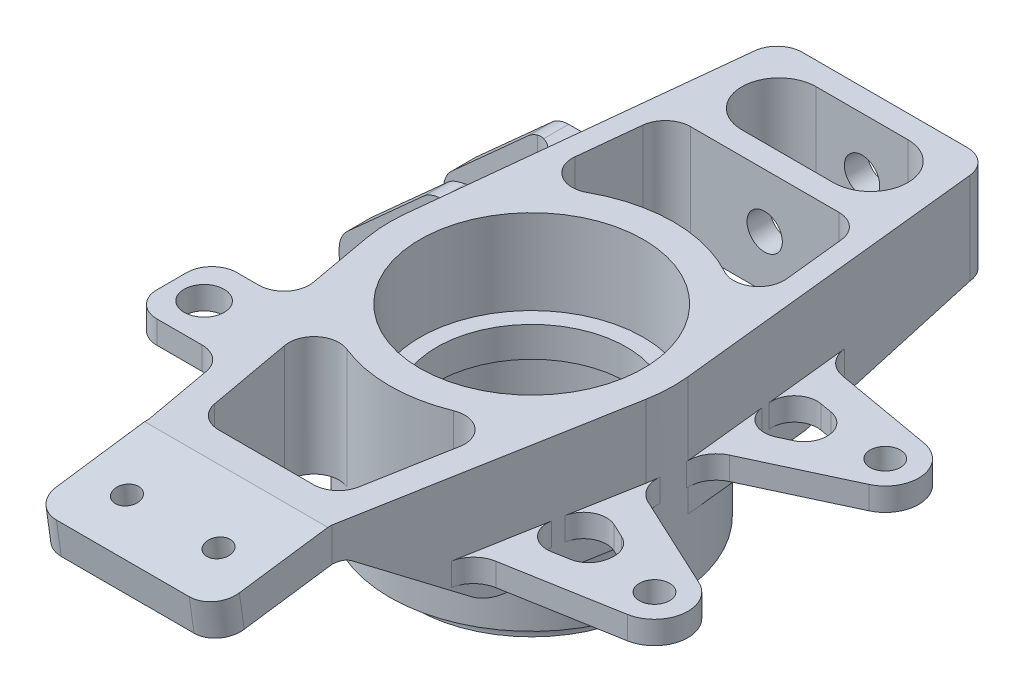
SolidWorks part; units mm, degrees
material "6061-T6 (SS)"
ref_plane "Front Plane" through (0, 0, 0) normal (0, 0, 1) x (1, 0, 0)
ref_plane "Top Plane" through (0, 0, 0) normal (0, 1, 0) x (1, 0, 0)
ref_plane "Right Plane" through (0, 0, 0) normal (1, 0, 0) x (0, 0, -1)
sketch "UBJ LBJ Geometry" plane through (0, 0, 0) normal (1, 0, 0) x (0, 0, -1)
  line L0 (0, 0) -> (0, -97.4059) construction
  line L1 (0, 0) -> (-30.7529, 0) construction
  line L2 (0, 22) -> (-45.5659, 22) construction
  line L3 (0, -10.5425) -> (-23.1063, -10.5425) construction
  line L4 (-94.107, -51.66) -> (81.28, -25.498) construction
  line L5 (0, 0) -> (0, -88.2735) construction
  line L6 (38.1, 0) -> (38.1, -66.9417) construction
  circle A0 centre (-94.107, -51.66) radius 10.3251 construction
  circle A1 centre (81.28, -25.498) radius 10.3251 construction
  dimension "D7" = 20.6502
  dimension "D8" = 20.6502
  dimension "D1" = 22
  dimension "D2" = 32.5425
  dimension "D3" = 47.498
  dimension "D4" = 73.66
  dimension "D5" = 94.107
  dimension "D6" = 81.28
  dimension "D9" = 38.1
ref_plane "Wheel Face " through (0, 22, 0) normal (0, -1, 0) x (-1, 0, 0)
ref_plane "Upright Face" through (0, -10.5425, 0) normal (0, -1, 0) x (-1, 0, 0)
ref_plane "Tie Bracket Plane" through (0, 0, -38.1) normal (0, 0, 1) x (1, 0, 0)
sketch "Tie Bracket Geometry" plane through (0, 0, -38.1) normal (0, 0, 1) x (1, 0, 0)
  line L0 (0, -31.939) -> (-65.5359, -45.8691) construction
  line L4 (0, 200000) -> (0, -200097.4059) construction
  circle A0 centre (-65.5359, -45.8691) radius 8.948 construction
  dimension "D1" = 67
  dimension "D2" = 78
sketch "Sketch1" plane through (0, 0, 0) normal (0, 0, 1) x (1, 0, 0)
  line L1 (-75.0953, -10.5425) -> (75.0953, -10.5425) construction
  line L2 (-39.37, -10.5425) -> (-39.37, -61.3425)
  line L3 (-39.37, -61.3425) -> (-32.258, -61.3425)
  line L4 (-32.258, -61.3425) -> (-32.258, -67.6925)
  line L5 (-32.258, -67.6925) -> (-30.9829, -67.6925)
  line L8 (-30.9829, -10.5425) -> (-30.9829, -34.0375)
  line L9 (-30.9829, -34.0375) -> (-26.289, -34.0375)
  line L10 (-26.289, -34.0375) -> (-26.289, -42.4195)
  line L11 (-26.289, -42.4195) -> (-30.9829, -42.4195)
  line L12 (-30.9829, -42.4195) -> (-30.9829, -67.6925)
  line L15 (-39.37, -10.5425) -> (-30.9829, -10.5425)
  line L17 (0, 0) -> (0, -23.5057) construction
  dimension "D1" = 8.382
  dimension "D2" = 61.9658
  dimension "D3" = 25.273
  dimension "D4" = 52.578
  dimension "D5" = 23.495
  dimension "D6" = 50.8
  dimension "D7" = 78.74
  dimension "D8" = 64.516
revolve "Bearing Housing Revolve" add sketch "Sketch1" angle 360 about L17
fillet "Bearing Housing Fillet" radius 6.35 1 edges at (0, -61.3425, 32.258)
sketch "Sketch2" plane through (0, -10.5425, 0) normal (0, -1, 0) x (-1, 0, 0)
  line L3 (39.37, -40.64) -> (39.37, 0)
  line L4 (-39.37, -40.64) -> (-39.37, 0)
  line L5 (39.37, -40.64) -> (-39.37, -40.64)
  circle A4 centre (0, 0) radius 39.37 construction
  arc A5 (39.37, 0) -> (-39.37, 0) centre (0, 0) cw
  dimension "D1" = 40.64
extrude "UBJ Prep" add sketch "Sketch2" along normal blind 33.02
sketch "Sketch3" plane through (-39.37, 0, 0) normal (-1, 0, 0) x (0, 0, 1)
  line L0 (-120.7672, 22) -> (120.7672, 22) construction
  line L1 (40.64, -10.5425) -> (81.931, -10.5425)
  line L2 (81.931, -10.5425) -> (113.372, -14.9612)
  line L3 (113.372, -14.9612) -> (112.0463, -24.3935)
  line L4 (112.0463, -24.3935) -> (80.6053, -19.9748)
  line L6 (40.64, -43.5625) -> (40.64, -10.5425)
  line L7 (81.931, -10.5425) -> (80.6053, -19.9748) construction
  line L8 (98.2025, -22.5188) -> (94.107, -51.66) construction
  line L9 (48.0448, -41.1804) -> (76.0192, -21.104)
  circle A0 centre (94.107, -51.66) radius 13.6189 construction
  arc A1 (40.64, -43.5625) -> (48.0448, -41.1804) centre (40.64, -30.8625) ccw
  arc A2 (80.6053, -19.9748) -> (76.0192, -21.104) centre (79.7216, -26.263) ccw
  dimension "D7" = 12.7
  dimension "D8" = 25.4
  dimension "D1" = 73.66
  dimension "D2" = 94.107
  dimension "D3" = 9.525
  dimension "D4" = 31.75
  dimension "D5" = 8
  dimension "D6" = 13.97
extrude "UBJ Extrude " add sketch "Sketch3" against normal up to surface (78.74 mm away) up to face at (39.37, -27.0525, 20.32)
sketch "Sketch4" plane through (0, -8.479, -1.1916) normal (0, -0.9903, -0.1392) x (1, 0, 0)
  line L0 (0, 114.3508) -> (0, 27.8969) construction
  line L1 (39.37, 114.3508) -> (-39.37, 114.3508) construction
  line L3 (-12.7, 100.3808) -> (12.7, 100.3808) construction
  circle A0 centre (-12.7, 100.3808) radius 3.2639
  circle A1 centre (12.7, 100.3808) radius 3.2639
  point P8 (0, 100.3808)
  dimension "D2" = 6.5278
  dimension "D1" = 25.4
  dimension "D3" = 13.97
extrude "Camber Block Holes" cut sketch "Sketch4" against normal up to surface (9.525 mm away) up to face at (0, -12.7519, 97.6515)
sketch "Sketch5" plane through (0, -43.5625, 0) normal (0, -1, 0) x (1, 0, 0)
  line L0 (-25.4, 112.0463) -> (-25.4, 80.8043)
  line L1 (25.4, 113.372) -> (39.37, 113.372)
  line L2 (39.37, 112.0463) -> (-39.37, 112.0463) construction
  line L4 (-25.4, 80.8043) -> (-38.742, 7.004)
  line L5 (25.4, 112.0463) -> (25.4, 80.8043)
  line L6 (25.4, 80.8043) -> (38.742, 7.004)
  line L7 (-25.4, 112.0463) -> (-25.4, 113.372)
  line L8 (39.37, 113.372) -> (-39.37, 113.372) construction
  line L9 (25.4, 112.0463) -> (25.4, 113.372)
  line L10 (-25.4, 113.372) -> (-39.37, 113.372)
  line L11 (-39.37, 113.372) -> (-39.37, 0)
  line L12 (39.37, 113.372) -> (39.37, 0)
  line L13 (-18.9481, 73.66) -> (18.9481, 73.66)
  line L14 (-18.9481, 73.66) -> (-27.1021, 28.5565)
  line L15 (18.9481, 73.66) -> (27.1021, 28.5565)
  arc A0 (-39.37, 0) -> (-38.742, 7.004) centre (0, 0) cw
  circle A1 centre (0, 0) radius 39.37 construction
  arc A2 (39.37, 0) -> (-39.37, 0) centre (0, 0) ccw construction
  arc A3 (39.37, 0) -> (38.742, 7.004) centre (0, 0) ccw
  arc A4 (-27.1021, 28.5565) -> (27.1021, 28.5565) centre (0, 0) cw
  point P31 (0, 73.66)
  dimension "D1" = 25.4
  dimension "D2" = 7.62
  dimension "D3" = 31.242
  dimension "D4" = 73.66
extrude "Weight Saving" cut sketch "Sketch5" against normal through all
fillet "Fillet2" radius 6.985 4 edges at (27.1021, -27.0525, 28.5565) (-27.1021, -27.0525, 28.5565) (18.9481, -16.6698, 73.66) (-18.9481, -16.6698, 73.66)
sketch "Sketch6" plane through (0, -10.5425, 0) normal (0, -1, 0) x (-1, 0, 0)
  line L0 (-39.37, 0) -> (-39.37, 40.64)
  line L1 (-39.37, 40.64) -> (39.37, 40.64)
  line L2 (39.37, 40.64) -> (39.37, 0)
  circle A0 centre (0, 0) radius 39.37 construction
  arc A1 (-39.37, 0) -> (39.37, 0) centre (0, 0) cw
  dimension "D1" = 40.64
extrude "LBJ Prep" add sketch "Sketch6" along normal blind 33.02
sketch "Sketch8" plane through (-39.37, 0, 0) normal (-1, 0, 0) x (0, 0, 1)
  line L0 (-40.64, -10.5425) -> (-97.9551, -10.5425)
  line L1 (-97.9551, -10.5425) -> (-97.9551, -35.9425)
  line L2 (-97.9551, -35.9425) -> (-91.6051, -35.9425)
  line L7 (-40.64, -43.5625) -> (-40.64, -10.5425)
  line L8 (-120.7672, 22) -> (120.7672, 22) construction
  line L9 (-91.6051, -35.9425) -> (-91.6051, -10.5425) construction
  line L10 (-91.6051, -35.9425) -> (-40.64, -43.5625)
  circle A0 centre (-81.28, -25.498) radius 10.3251 construction
  dimension "D3" = 20.6502
  dimension "D1" = 81.28
  dimension "D2" = 47.498
  dimension "D4" = 6.35
  dimension "D5" = 25.4
extrude "LBJ Area " add sketch "Sketch8" against normal up to surface (78.74 mm away) up to face at (39.37, -27.0525, -20.32)
sketch "Sketch7" plane through (0, -43.5625, 0) normal (0, -1, 0) x (1, 0, 0)
  line L0 (-12.7, -81.28) -> (12.7, -81.28) construction
  line L1 (0, -200000) -> (0, 200045.5659) construction
  line L2 (-12.7, -70.9549) -> (12.7, -70.9549)
  line L3 (-12.7, -91.6051) -> (12.7, -91.6051)
  line L4 (-29.21, -97.9551) -> (-39.1508, -4.1489)
  line L5 (39.37, -97.9551) -> (-39.37, -97.9551) construction
  line L6 (29.21, -97.9551) -> (39.1508, -4.1489)
  line L7 (-29.21, -97.9551) -> (-39.37, -97.9551)
  line L8 (-39.37, -97.9551) -> (-39.37, 0)
  line L9 (29.21, -97.9551) -> (39.37, -97.9551)
  line L10 (39.37, -97.9551) -> (39.37, 0)
  line L13 (-26.8695, -64.6049) -> (26.8695, -64.6049)
  line L14 (26.8695, -64.6049) -> (31.1666, -24.0549)
  line L15 (-26.8695, -64.6049) -> (-31.1666, -24.0549)
  arc A0 (-12.7, -70.9549) -> (-12.7, -91.6051) centre (-12.7, -81.28) ccw
  arc A1 (12.7, -91.6051) -> (12.7, -70.9549) centre (12.7, -81.28) ccw
  circle A2 centre (0, 0) radius 39.37 construction
  arc A3 (-39.37, 0) -> (39.37, 0) centre (0, 0) ccw construction
  arc A4 (39.37, 0) -> (39.1508, -4.1489) centre (0, 0) cw
  arc A5 (-39.37, 0) -> (-39.1508, -4.1489) centre (0, 0) ccw
  arc A6 (-31.1666, -24.0549) -> (31.1666, -24.0549) centre (0, 0) ccw
  point P4 (0, -81.28)
  point P28 (0, -64.6049)
  dimension "D1" = 81.28
  dimension "D2" = 20.6502
  dimension "D3" = 25.4
  dimension "D4" = 10.16
  dimension "D5" = 6.35
  dimension "D6" = 5.842
extrude "LBJ Taper And Slot" cut sketch "Sketch7" against normal up to surface (33.02 mm away) up to face at (0, -10.5425, 14.3596)
fillet "Fillet3" radius 6.985 4 edges at (26.8695, -25.2609, -64.6049) (-26.8695, -25.2609, -64.6049) (31.1666, -27.0525, -24.0549) (-31.1666, -27.0525, -24.0549)
extrude "LBJ Holes 3/8 Clearance" cut sketch "Sketch9" against normal up to surface (33.3502 mm away) up to face at (0, -25.2609, -64.6049)
sketch "Sketch9" plane through (0, 0, -97.9551) normal (0, 0, -1) x (-1, 0, 0)
  circle A0 centre (0, -25.498) radius 4.9022
  dimension "D2" = 9.8044
  dimension "D1" = 25.498
ref_plane "Brake Mounting Plane" through (0, -30.7025, 0) normal (0, 1, 0) x (1, 0, 0)
sketch "Sketch10" plane through (0, -30.7025, 0) normal (0, 1, 0) x (1, 0, 0)
  line L0 (87.9814, 0) -> (161.3053, 0) construction
  line L1 (0, 72.9505) -> (0, 47.1638) construction
  line L2 (66.04, 32) -> (66.04, -32) construction
  line L3 (69.9619, 23.5895) -> (38.6385, 8.9831)
  line L4 (39.1508, 4.1489) -> (29.21, 97.9551) construction
  line L5 (38.6385, 8.9831) -> (34.6135, 46.9645)
  line L6 (34.6135, 46.9645) -> (67.6515, 41.139)
  line L7 (69.9619, -23.5895) -> (38.404, -8.8738)
  line L8 (25.4, -80.8043) -> (38.742, -7.004) construction
  line L9 (38.404, -8.8738) -> (31.4158, -47.5283)
  line L10 (31.4158, -47.5283) -> (67.6515, -41.139)
  circle A0 centre (66.04, 32) radius 4.2
  circle A1 centre (66.04, -32) radius 4.2
  arc A2 (67.6515, -41.139) -> (69.9619, -23.5895) centre (66.04, -32) ccw
  arc A3 (69.9619, 23.5895) -> (67.6515, 41.139) centre (66.04, 32) ccw
  point P7 (66.04, 0)
  dimension "D2" = 8.4
  dimension "D3" = 5.08
  dimension "D4" = 5.08
  dimension "D1" = 64
  dimension "D5" = 66.04
  dimension "D6" = 80
  dimension "D7" = 65
  dimension "D8" = 65
  dimension "D9" = 100
extrude "Brake Mounts" add sketch "Sketch10" against normal blind 6.35
fillet "Outside Fillets" radius 7.62 4 edges at (38.404, -33.8775, 8.8738) (31.4158, -33.8775, 47.5283) (38.6385, -33.8775, -8.9831) (34.6135, -33.8775, -46.9645)
sketch "Sketch18" plane through (0, -37.0525, 0) normal (0, -1, 0) x (1, 0, 0)
  line L0 (33.1015, 38.204) -> (36.7685, 17.9202)
  line L1 (36.7685, 17.9202) -> (52.8827, 25.4343)
  line L2 (52.8827, 25.4343) -> (50.6114, 35.1165)
  line L3 (50.6114, 35.1165) -> (33.1015, 38.204)
  line L4 (37.648, -18.3303) -> (35.5884, -37.7655)
  line L5 (35.5884, -37.7655) -> (53.0983, -34.678)
  line L6 (53.0983, -34.678) -> (52.1507, -25.093)
  line L7 (52.1507, -25.093) -> (37.648, -18.3303)
  line L8 (34.009, -52.6695) -> (39.1508, -4.1489) construction
  line L9 (38.742, 7.004) -> (30.4709, 52.7547) construction
  line L10 (69.9619, 23.5895) -> (43.5656, 11.2807) construction
  line L11 (36.6462, 46.6061) -> (67.6515, 41.139) construction
  line L12 (43.5656, -11.2807) -> (69.9619, -23.5895) construction
  line L13 (67.6515, -41.139) -> (40.2634, -45.9683) construction
  dimension "D1" = 8.89
  dimension "D2" = 8.89
  dimension "D3" = 8.89
  dimension "D4" = 8.89
  dimension "D5" = 17.78
  dimension "D6" = 17.78
  dimension "D7" = 16.002
  dimension "D8" = 17.78
extrude "Inside Holes" cut sketch "Sketch18" against normal up to surface (6.35 mm away) up to face at (66.04, -30.7025, 36.2)
fillet "Inside Fillet" radius 6.35 8 edges at (35.5884, -33.8775, -37.7655) (53.0983, -33.8775, -34.678) (52.1507, -33.8775, -25.093) (37.648, -33.8775, -18.3303) (36.7685, -33.8775, 17.9202) (33.1015, -33.8775, 38.204) (52.8827, -33.8775, 25.4343) (50.6114, -33.8775, 35.1165)
sketch "Sketch12" plane through (0, 0, -38.1) normal (0, 0, 1) x (1, 0, 0)
  line L0 (0, 3.2946) -> (0, -38.5659) construction
  line L1 (-90.5661, 0) -> (-38.2005, 0) construction
  line L2 (-73.702, -10.5425) -> (-73.702, -45.8691)
  line L3 (-57.3698, -10.5425) -> (-57.3698, -45.8691)
  line L4 (-73.702, -10.5425) -> (-57.3698, -10.5425)
  line L6 (-75.0953, -10.5425) -> (75.0953, -10.5425) construction
  circle A0 centre (-65.5359, -45.8691) radius 3.2639
  arc A1 (-73.702, -45.8691) -> (-57.3698, -45.8691) centre (-65.5359, -45.8691) ccw
  dimension "D1" = 6.5278
  dimension "D2" = 4.9022
extrude "Initial Toe Bracket" add sketch "Sketch12" along normal blind 17.78 and the other way blind 17.78 separate body
sketch "Sketch13" plane through (-57.3698, 0, 0) normal (1, 0, 0) x (0, 0, -1)
  line L0 (20.32, -18.1625) -> (55.88, -18.1625)
  line L1 (55.88, -45.8691) -> (55.88, -10.5425) construction
  line L2 (55.88, -18.1625) -> (55.88, -38.4825)
  line L3 (20.32, -18.1625) -> (20.32, -38.4825)
  line L4 (200000, -10.5425) -> (-200023.1063, -10.5425) construction
  line L5 (20.32, -38.4825) -> (55.88, -38.4825)
  line L6 (20.32, -45.8691) -> (20.32, -10.5425) construction
  dimension "D1" = 7.62
  dimension "D2" = 20.32
extrude "Toe Bracket Connection to Upright" add sketch "Sketch13" along normal up to surface (23.701 mm away) up to face at (-33.648, -30.0158, -56.0755)
sketch "Sketch14" plane through (0, 0, -55.88) normal (0, 0, -1) x (-1, 0, 0)
  line L1 (57.3698, -10.5425) -> (73.702, -10.5425)
  line L2 (57.3698, -10.5425) -> (57.3698, -18.1625)
  line L3 (57.3698, -18.1625) -> (73.702, -18.1625)
  line L4 (73.702, -10.5425) -> (73.702, -18.1625)
  line L5 (73.702, -10.5425) -> (73.702, -45.8691) construction
extrude "Excess Toe Bracket Cut" cut sketch "Sketch14" against normal up to surface (35.56 mm away) up to face at (-56.4697, -29.2849, -20.32)
sketch "Sketch21" plane through (0, 0, -20.32) normal (0, 0, 1) x (1, 0, 0)
  line L1 (-39.37, -10.5425) -> (-39.37, -61.3425) construction
  line L2 (-46.355, -38.4825) -> (-57.3698, -38.4825)
  line L3 (-57.3698, -38.4825) -> (-59.8151, -51.6965)
  line L4 (-59.8151, -51.6965) -> (-46.355, -38.4825)
  arc A0 (-73.702, -45.8691) -> (-57.3698, -45.8691) centre (-65.5359, -45.8691) ccw construction
  dimension "D1" = 6.985
extrude "Extra Material" add sketch "Sketch21" against normal up to surface (35.56 mm away) up to face at (-54.9135, -35.5324, -55.88)
sketch "Sketch23" plane through (-73.702, 0, 0) normal (-1, 0, 0) x (0, 0, 1)
  line L2 (-38.1, -4.9367) -> (-38.1, -40.1578) construction
  line L4 (-20.32, -18.1625) -> (-55.88, -18.1625) construction
  line L5 (-49.276, -18.1625) -> (-26.924, -18.1625)
  line L6 (-26.924, -18.1625) -> (-26.924, -66.0195)
  line L7 (-26.924, -66.0195) -> (-49.276, -66.0195)
  line L8 (-49.276, -66.0195) -> (-49.276, -18.1625)
  point P4 (-38.1, -18.1625)
  point P10 (-38.1, -18.1625)
  dimension "D1" = 22.352
extrude "Slot Clearning" cut sketch "Sketch23" against normal blind 33.02
sketch "Sketch26" plane through (0, 0, -20.32) normal (0, 0, 1) x (1, 0, 0)
  line L0 (-73.702, -41.0225) -> (-48.302, -18.1625)
  line L1 (-73.702, -18.1625) -> (-73.702, -45.8691) construction
  line L2 (-37.4371, -18.1625) -> (-73.702, -18.1625) construction
  line L3 (-48.302, -18.1625) -> (-73.702, -18.1625)
  line L4 (-73.702, -18.1625) -> (-73.702, -41.0225)
  circle A0 centre (-65.5359, -45.8691) radius 8.1661 construction
  arc A1 (-73.702, -45.8691) -> (-59.8151, -51.6965) centre (-65.5359, -45.8691) ccw construction
  dimension "D1" = 22.86
  dimension "D2" = 25.4
extrude "Cut-Extrude3" cut sketch "Sketch26" against normal up to surface (35.56 mm away) up to face at (-53.8081, -35.912, -55.88)
fillet "Toe Bracket Fillet" radius 6.985 2 edges at (-33.6688, -28.3225, -55.88) (-37.4371, -28.3225, -20.32)
sketch "Sketch19" plane through (0, -18.1625, 0) normal (0, 1, 0) x (1, 0, 0)
  line L0 (0, 38.1) -> (-65.5359, 38.1) construction
  circle A0 centre (-35.4919, 38.1) radius 6.35
  arc A6 (-39.1508, 4.1489) -> (-38.742, -7.004) centre (0, 0) ccw construction
  dimension "D1" = 12.7
  dimension "D2" = 6.35
fillet "Inside Toe Fillet" radius 6.985 2 edges at (-40.682, -28.3225, -49.276) (-40.682, -28.3225, -26.924)
fillet "Fillet9" radius 6.985 4 edges at (-73.702, -41.0225, -23.622) (-73.702, -41.0225, -52.578) (-48.302, -18.1625, -52.578) (-48.302, -18.1625, -23.622)
fillet "Fillet5" radius 6.985 4 edges at (-25.4, -19.6774, 112.7092) (25.4, -19.6774, 112.7092) (29.21, -23.2425, -97.9551) (-29.21, -23.2425, -97.9551)
sketch "Sketch17" plane through (0, -10.5425, 0) normal (0, 1, 0) x (1, 0, 0)
  line L0 (-33.9813, -33.3375) -> (-55.3633, -33.3375)
  line L1 (-38.742, -7.004) -> (-25.4, -80.8043) construction
  line L2 (-55.3633, -33.3375) -> (-55.3633, -55.5625)
  line L3 (-55.3633, -55.5625) -> (-29.9633, -55.5625)
  line L4 (-33.9813, -33.3375) -> (-29.9633, -55.5625)
  circle A0 centre (-46.2352, -44.45) radius 5.9531
  circle A1 centre (-46.2352, -44.45) radius 18.3654 construction
  circle A2 centre (-46.2352, -44.45) radius 10.3251 construction
  point P7 (-55.3633, -44.45)
  dimension "D2" = 3.175
  dimension "D5" = 11.9062
  dimension "D6" = 20.6502
  dimension "D1" = 44.45
  dimension "D3" = 22.225
  dimension "D4" = 25.4
extrude "EXtrude Mount Start" add sketch "Sketch17" against normal blind 6.35
thread "Speed Sensor Mount" pitch 0.9071 method cut profile "Thread Profile1" start angle 0, offset 0, length 10, pitch 0.7937, diameter 11.9062
ref_plane "Plane1" through (-52.1883, -10.5425, 44.45) normal (0, 0, 1) x (-1, 0, 0)
sketch "Thread Profile1" plane through (-52.1883, -10.5425, 44.45) normal (0, 0, 1) x (-1, 0, 0)
  line L0 (0, 0) -> (0, 0.9071) construction
  line L1 (0, 0) -> (0.491, 0.2835)
  line L2 (0.491, 0.2835) -> (0.491, 0.3969)
  line L3 (0.491, 0.3969) -> (0, 0.6804)
  line L4 (0.491, 0.3402) -> (0, 0.3402) construction
  line L11 (0, 0) -> (0, 0.6804)
  point P2 (0, 0)
  dimension "Pitch" = 0.9071
  dimension "Profile_Angle" = 60
  dimension "Profile_Land" = 0.1134
  dimension "Profile_Height" = 0.491
fillet "Fillet7" radius 6.985 4 edges at (-55.3633, -13.7175, 55.5625) (-55.3633, -13.7175, 33.3375) (-33.9813, -13.7175, 33.3375) (-29.9633, -13.7175, 55.5625)
sketch "Sketch27" plane through (0, 0, -97.9551) normal (0, 0, -1) x (-1, 0, 0)
  line L0 (-75.32, -33.8775) -> (73.899, -33.8775) construction
  line L1 (-75.32, -30.7025) -> (-75.32, -37.0525) construction
  line L2 (73.899, -16.0888) -> (73.899, -54.8637) construction
sketch "Sketch28" plane through (0, -16.8925, 0) normal (0, -1, 0) x (1, 0, 0)
  circle A0 centre (-46.1628, 44.6715) radius 5.5562
  circle A1 centre (-46.1628, 44.6715) radius 7.0988
  dimension "D1" = 11.1125
extrude "Boss-Extrude1" add sketch "Sketch28" against normal up to surface (6.35 mm away) up to face at (-17.4973, -10.5425, 15.1349)
equation "\"Wheel_Offset\"= 22mm"
equation "\"HUB_to_UBJ_Lat\"= 2.9in"
equation "\"Hub_to_UBJ_Vert\"= 3.705in"
equation "\"Hub_to_LBJ_Lat\"= 1.87in"
equation "\"Hub_to_LBJ_Vert\"= 3.2in"
equation "\"Wheel_face_to_Upright_back\"= 1.2812in'This is the distance between the whee face to the upright back."
equation "\"UBJ_Angle\"= 8deg"
equation "\"D2@UBJ LBJ Geometry\" = \"Wheel_face_to_Upright_back\""
equation "\"D3@UBJ LBJ Geometry\" = \"Hub_to_LBJ_Lat\""
equation "\"D4@UBJ LBJ Geometry\" = \"HUB_to_UBJ_Lat\""
equation "\"D5@UBJ LBJ Geometry\" = \"Hub_to_UBJ_Vert\""
equation "\"D6@UBJ LBJ Geometry\" = \"Hub_to_LBJ_Vert\""
equation "\"D1@Sketch3\"=\"HUB_to_UBJ_Lat\""
equation "\"D2@Sketch3\"=\"Hub_to_UBJ_Vert\""
equation "\"D1@Sketch8\"=\"Hub_to_LBJ_Vert\""
equation "\"D2@Sketch8\"=\"Hub_to_LBJ_Lat\""
equation "\"Hub_Tie_Bracket_Vert\"= 1.6'(Not Given) Ask Sus and Controls later"
equation "\"Tie_Beta\"= 12deg'From FE11 Master"
equation "\"Toe_Arm\"= 67mm'From FE11 Master (Assume Dist start at KPI)"
equation "\"D1@Sketch7\"=\"Hub_to_LBJ_Vert\""
equation "\"D1@Sketch9\"=\"Hub_to_LBJ_Lat\"-\"Wheel_Offset\""
equation "\"D1@Tie Bracket Geometry\" = \"Toe_Arm\""
equation "\"D2@Tie Bracket Geometry\" = 90 - \"Tie_Beta\""
equation "\"D5@Sketch3\"=\"UBJ_Angle\""
equation "\"D1@Sketch7\"=\"Hub_to_LBJ_Lat\""
